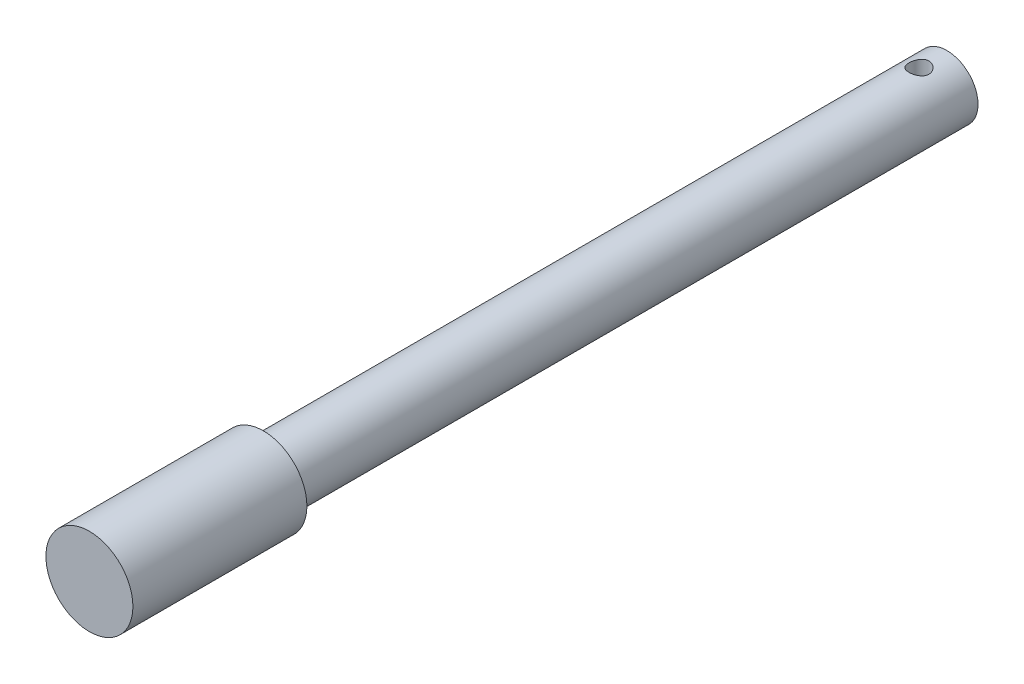
SolidWorks part; units mm, degrees
ref_plane "Front Plane" through (0, 0, 0) normal (0, 0, 1) x (1, 0, 0)
ref_plane "Top Plane" through (0, 0, 0) normal (0, 1, 0) x (1, 0, 0)
ref_plane "Right Plane" through (0, 0, 0) normal (1, 0, 0) x (0, 0, -1)
sketch "Sketch1" plane through (0, 0, 0) normal (0, 0, 1) x (1, 0, 0)
  circle A0 centre (0, 0) radius 10
  dimension "D1" = 20
extrude "Boss-Extrude1" add sketch "Sketch1" along normal blind 276 contours A0
sketch "Sketch2" plane through (0, 0, 276) normal (0, 0, 1) x (1, 0, 0)
  circle A0 centre (0, 0) radius 14
extrude "Boss-Extrude2" add sketch "Sketch2" against normal blind 56
sketch "Sketch3" plane through (0, 0, 0) normal (0, 1, 0) x (1, 0, 0)
  line L0 (10, 0) -> (-10, 0) construction
  line L1 (-10, 0) -> (-10, -220) construction
  circle A0 centre (0, -9) radius 3.2
  dimension "D1" = 9
  dimension "D2" = 10
extrude "Cut-Extrude1" cut sketch "Sketch3" against normal blind 56 and the other way blind 56
